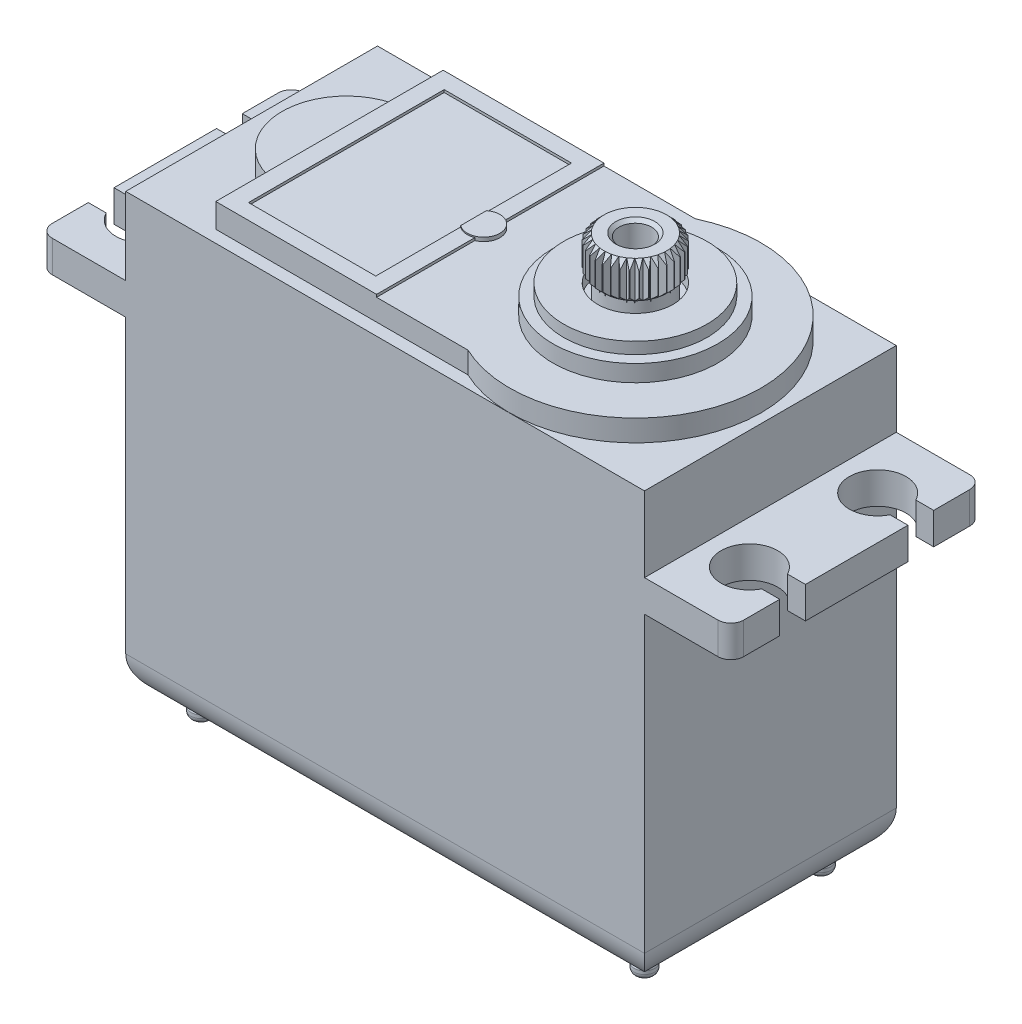
SolidWorks part; units mm, degrees
ref_plane "Front Plane" through (0, 0, 0) normal (0, 0, 1) x (1, 0, 0)
ref_plane "Top Plane" through (0, 0, 0) normal (0, 1, 0) x (1, 0, 0)
ref_plane "Right Plane" through (0, 0, 0) normal (1, 0, 0) x (0, 0, -1)
sketch "Sketch1" plane through (0, 0, 0) normal (0, 1, 0) x (1, 0, 0)
  line L1 (-18.6567, 11.3793) -> (21.6633, 11.3793)
  line L2 (-18.6567, 11.3793) -> (-18.6567, -8.1907)
  line L3 (-18.6567, -8.1907) -> (21.6633, -8.1907)
  line L4 (21.6633, 11.3793) -> (21.6633, -8.1907)
extrude "Boss-Extrude1" add sketch "Sketch1" along normal blind 35.37
sketch "Sketch2" plane through (21.6633, 0, 0) normal (1, 0, 0) x (0, 0, -1)
  line L0 (-8.1907, 0) -> (-8.1907, 3)
  line L1 (-8.1907, 35.37) -> (-8.1907, 0) construction
  line L2 (-8.1907, 3) -> (-5.1907, 0)
  line L3 (-8.1907, 0) -> (11.3793, 0) construction
  line L4 (-5.1907, 0) -> (-8.1907, 0)
  line L5 (1.5943, 0) -> (1.5943, 35.37) construction
  line L6 (-8.1907, 35.37) -> (11.3793, 35.37) construction
  line L7 (8.3793, 0) -> (11.3793, 0)
  line L8 (11.3793, 3) -> (8.3793, 0)
  line L9 (11.3793, 0) -> (11.3793, 3)
extrude "Cut-Extrude1" cut sketch "Sketch2" against normal up to next
sketch "Sketch3" plane through (0, 0, 8.1907) normal (0, 0, 1) x (1, 0, 0)
  line L0 (21.6633, 0) -> (18.6633, 0)
  line L1 (-18.6567, 0) -> (21.6633, 0) construction
  line L2 (18.6633, 0) -> (21.6633, 3)
  line L3 (21.6633, 35.37) -> (21.6633, 3) construction
  line L4 (21.6633, 3) -> (21.6633, 0)
  line L5 (1.5033, 35.37) -> (1.5033, 0) construction
  line L6 (-18.6567, 35.37) -> (21.6633, 35.37) construction
  line L7 (-18.6567, 3) -> (-18.6567, 0)
  line L8 (-15.6567, 0) -> (-18.6567, 3)
  line L9 (-18.6567, 0) -> (-15.6567, 0)
extrude "Cut-Extrude2" cut sketch "Sketch3" against normal up to next
fillet "Fillet2" radius 3 4 edges at (21.6633, 3, -1.5943) (1.5033, 3, 8.1907) (-18.6567, 3, -1.5943) (1.5033, 3, -11.3793)
sketch "Sketch5" plane through (21.6633, 0, 0) normal (1, 0, 0) x (0, 0, -1)
  line L0 (1.5943, 35.37) -> (1.5943, 29.53) construction
  line L1 (-8.1907, 35.37) -> (11.3793, 35.37) construction
  line L2 (-8.1907, 29.53) -> (1.5943, 29.53)
  line L3 (-8.1907, 35.37) -> (-8.1907, 4.2426) construction
  line L4 (1.5943, 29.53) -> (11.3793, 29.53)
  line L5 (11.3793, 35.37) -> (11.3793, 4.2426) construction
  line L6 (11.3793, 29.53) -> (11.3793, 27.07)
  line L7 (11.3793, 27.07) -> (-8.1907, 27.07)
  line L8 (-8.1907, 27.07) -> (-8.1907, 29.53)
extrude "Boss-Extrude2" add sketch "Sketch5" along normal blind 6.71
sketch "Sketch7" plane through (-18.6567, 0, 0) normal (-1, 0, 0) x (0, 0, 1)
  line L0 (-1.5943, 35.37) -> (-1.5943, 29.3613) construction
  line L1 (-11.3793, 29.3613) -> (-1.5943, 29.3613)
  line L2 (-1.5943, 29.3613) -> (8.1907, 29.3613)
  line L3 (8.1907, 29.3613) -> (8.1907, 26.9013)
  line L4 (8.1907, 26.9013) -> (-11.3793, 26.9013)
  line L5 (-11.3793, 26.9013) -> (-11.3793, 29.3613)
  line L6 (-11.3793, 35.37) -> (8.1907, 35.37) construction
  line L7 (8.1907, 35.37) -> (8.1907, 4.2426) construction
  line L8 (-11.3793, 35.37) -> (-11.3793, 4.2426) construction
extrude "Boss-Extrude3" add sketch "Sketch7" along normal blind 6.71
sketch "Sketch8" plane through (0, 29.53, 0) normal (0, 1, 0) x (1, 0, 0)
  line L0 (25.0183, 11.3793) -> (25.0183, 6.5793) construction
  line L1 (28.3733, 11.3793) -> (21.6633, 11.3793) construction
  line L2 (28.3733, 5.5793) -> (26.9779, 5.5793)
  line L3 (25.0183, -8.1907) -> (25.0183, -3.3907) construction
  line L4 (28.3733, -8.1907) -> (21.6633, -8.1907) construction
  line L5 (28.3733, 7.5793) -> (28.3733, 5.5793)
  line L6 (25.0183, 6.5793) -> (28.3733, 6.5793) construction
  line L7 (28.3733, 11.3793) -> (28.3733, -8.1907) construction
  line L8 (28.3733, 6.5793) -> (28.3733, 7.5793) construction
  line L9 (28.3733, 6.5793) -> (28.3733, 5.5793) construction
  line L10 (28.3733, 7.5793) -> (26.9779, 7.5793)
  line L11 (25.0183, -3.3907) -> (28.3733, -3.3907) construction
  line L12 (28.3733, -3.3907) -> (28.3733, -2.3907) construction
  line L13 (28.3733, -3.3907) -> (28.3733, -4.3907) construction
  line L14 (28.3733, -2.3907) -> (26.9779, -2.3907)
  line L15 (28.3733, -4.3907) -> (26.9779, -4.3907)
  line L16 (28.3733, -2.3907) -> (28.3733, -4.3907)
  line L17 (0, 0) -> (1.5, 0) construction
  line L18 (1.5, 0) -> (1.5, -13.7092) construction
  line L19 (-25.3733, -3.3907) -> (-25.3733, -4.3907) construction
  line L20 (-25.3733, -3.3907) -> (-25.3733, -2.3907) construction
  line L21 (-22.0183, -3.3907) -> (-25.3733, -3.3907) construction
  line L22 (-25.3733, 6.5793) -> (-25.3733, 5.5793) construction
  line L23 (-25.3733, 6.5793) -> (-25.3733, 7.5793) construction
  line L24 (-22.0183, 6.5793) -> (-25.3733, 6.5793) construction
  line L25 (-22.0183, -8.1907) -> (-22.0183, -3.3907) construction
  line L26 (-22.0183, 11.3793) -> (-22.0183, 6.5793) construction
  line L27 (-25.3733, -2.3907) -> (-25.3733, -4.3907)
  line L28 (-25.3733, -4.3907) -> (-23.9779, -4.3907)
  line L29 (-25.3733, -2.3907) -> (-23.9779, -2.3907)
  line L30 (-25.3733, 7.5793) -> (-23.9779, 7.5793)
  line L31 (-25.3733, 7.5793) -> (-25.3733, 5.5793)
  line L32 (-25.3733, 5.5793) -> (-23.9779, 5.5793)
  line L33 (-22.0183, 6.5793) -> (25.0183, 6.5793) construction
  line L34 (-19.8183, -3.3907) -> (-18.6668, -3.3907) construction
  line L35 (-22.0183, 6.5793) -> (-22.0183, -3.3907) construction
  line L38 (-22.0183, 6.5793) -> (25.0183, -3.3907) construction
  line L39 (-22.0183, -3.3907) -> (25.0183, 6.5793) construction
  line L40 (-25.3733, -8.1907) -> (28.3733, -8.1907) construction
  arc A0 (26.9779, 7.5793) -> (26.9779, 5.5793) centre (25.0183, 6.5793) ccw
  arc A1 (26.9779, -2.3907) -> (26.9779, -4.3907) centre (25.0183, -3.3907) ccw
  arc A2 (-23.9779, -2.3907) -> (-23.9779, -4.3907) centre (-22.0183, -3.3907) cw
  arc A3 (-23.9779, 7.5793) -> (-23.9779, 5.5793) centre (-22.0183, 6.5793) cw
  point P39 (1.5, 1.5943)
  dimension "D1" = 47.0366
  dimension "D2" = 9.97
  dimension "D3" = 53.7466
extrude "Cut-Extrude3" cut sketch "Sketch8" against normal up to next
sketch "Sketch9" plane through (0, 35.37, 0) normal (0, 1, 0) x (1, 0, 0)
  line L0 (6.9933, -8.1907) -> (6.9933, -7.2426) construction
  line L1 (-18.6567, 6.4311) -> (-12.6067, 6.4311) construction
  line L2 (6.9933, 11.3793) -> (6.9933, 10.4311) construction
  line L3 (-18.6567, -3.2426) -> (-12.6067, -3.2426) construction
  line L4 (-18.6567, -8.1907) -> (-18.6567, 11.3793) construction
  line L5 (-18.6567, 1.5943) -> (21.6633, 1.5943) construction
  line L6 (-12.6067, 10.4311) -> (6.9933, 10.4311)
  line L7 (-18.6567, 11.3793) -> (-18.6567, -8.1907) construction
  line L8 (-12.6067, -7.2426) -> (-12.6067, -3.2426)
  line L9 (21.6633, -8.1907) -> (21.6633, 11.3793) construction
  line L10 (-12.6067, 10.4311) -> (-12.6067, 6.4311)
  line L11 (-12.6067, -7.2426) -> (6.9933, -7.2426)
  line L12 (21.6633, 1.5943) -> (20.9438, 1.5943) construction
  line L13 (21.6633, 11.3793) -> (-18.6567, 11.3793) construction
  arc A0 (6.9933, 10.4311) -> (6.9933, -7.2426) centre (11.1697, 1.5943) cw
  arc A1 (-12.6067, 6.4311) -> (-12.6067, -3.2426) centre (-11.2767, 1.5943) ccw
extrude "Boss-Extrude4" add sketch "Sketch9" along normal blind 1.67
sketch "Sketch10" plane through (0, 37.04, 0) normal (0, 1, 0) x (1, 0, 0)
  circle A1 centre (11.1697, 1.5943) radius 6.415
extrude "Boss-Extrude5" add sketch "Sketch10" along normal blind 1.3
sketch "Sketch11" plane through (0, 38.34, 0) normal (0, 1, 0) x (-1, 0, 0)
  circle A2 centre (-11.1697, -1.5943) radius 5.575
extrude "Boss-Extrude6" add sketch "Sketch11" along normal blind 0.9
sketch "Sketch12" plane through (0, 39.24, 0) normal (0, 1, 0) x (1, 0, 0)
  circle A1 centre (11.1697, 1.5943) radius 2.925
extrude "Cut-Extrude4" cut sketch "Sketch12" against normal blind 1
sketch "Sketch13" plane through (0, 38.24, 0) normal (0, 1, 0) x (-1, 0, 0)
  circle A0 centre (-11.1697, -1.5943) radius 2.425
extrude "Boss-Extrude7" add sketch "Sketch13" along normal blind 1.5
sketch "Sketch14" plane through (0, 39.74, 0) normal (0, 1, 0) x (1, 0, 0)
  circle A0 centre (11.1697, 1.5943) radius 2.925
extrude "Boss-Extrude8" add sketch "Sketch14" along normal blind 2.86
sketch "Sketch15" plane through (0, 42.6, 0) normal (0, 1, 0) x (1, 0, 0)
  circle A0 centre (11.1697, 1.5943) radius 1.27
extrude "Cut-Extrude5" cut sketch "Sketch15" against normal blind 7
sketch "Sketch16" plane through (0, 37.04, 0) normal (0, 1, 0) x (1, 0, 0)
  line L0 (-12.6067, -7.2426) -> (6.9933, -7.2426) construction
  line L1 (-12.6067, 10.4311) -> (-0.1067, 10.4311)
  line L2 (-12.6067, 10.4311) -> (-12.6067, -7.2426)
  line L3 (-12.6067, -7.2426) -> (-0.1067, -7.2426)
  line L4 (-0.1067, 10.4311) -> (-0.1067, -7.2426)
  line L5 (-6.3168, 9.1673) -> (-6.3567, 10.4311) construction
  line L6 (-11.2628, 9.1673) -> (-1.3708, 9.1673)
  line L7 (-11.2628, 9.1673) -> (-11.2628, -6.0433)
  line L8 (-11.2628, -6.0433) -> (-1.3708, -6.0433)
  line L9 (-1.3708, 9.1673) -> (-1.3708, 1.562)
  line L10 (-11.2628, 1.562) -> (-12.6067, 1.5943) construction
  line L11 (-1.3708, 1.562) -> (-0.1067, 1.5943) construction
  line L12 (-6.3168, -6.0433) -> (-6.3567, -7.2426) construction
  line L13 (-1.3708, 1.562) -> (-1.3708, -6.0433)
extrude "Boss-Extrude9" add sketch "Sketch16" along normal blind 0.2
sketch "Sketch17" plane through (0, 37.24, 0) normal (0, 1, 0) x (-1, 0, 0)
  line L0 (1.3708, -1.562) -> (1.3708, -2.562)
  line L1 (1.3708, 6.0433) -> (1.3708, -9.1673) construction
  line L2 (1.3708, -1.562) -> (1.3708, -0.562)
  arc A0 (1.3708, -2.562) -> (1.3708, -0.562) centre (0.592, -1.562) cw
extrude "Boss-Extrude10" add sketch "Sketch17" along normal blind 0.1 and the other way blind 0.5
sketch "Sketch19" plane through (0, 42.6, 0) normal (0, 1, 0) x (1, 0, 0)
  line L0 (10.8404, 4.5007) -> (11.3402, 4.5143) construction
  line L1 (11.3402, 4.5143) -> (11.0903, 4.0075)
  line L2 (11.0903, 4.0075) -> (10.8404, 4.5007)
  line L3 (11.0903, 4.5075) -> (11.0903, 4.0075) construction
  line L4 (10.8404, 4.5007) -> (10.7613, 4.6463)
  line L5 (11.3402, 4.5143) -> (11.4053, 4.6463)
  line L6 (10.7613, 4.6463) -> (11.4053, 4.6463)
  circle A3 centre (11.1697, 1.5943) radius 2.925 construction
  circle A4 centre (11.1697, 1.5943) radius 2.925 construction
extrude "Cut-Extrude11" cut sketch "Sketch19" against normal blind 3
sketch "Sketch21" plane through (0, 0, 0) normal (0, -1, 0) x (1, 0, 0)
  line L0 (1.5033, 5.1907) -> (1.5033, -8.3793) construction
  line L1 (20.7846, 7.3121) -> (17.7846, 7.3121)
  line L2 (20.7846, 7.3121) -> (20.7846, 4.3121)
  line L3 (20.7846, 4.3121) -> (17.7846, 4.3121)
  line L4 (17.7846, 7.3121) -> (17.7846, 4.3121)
  line L5 (-15.6567, 5.1907) -> (18.6633, 5.1907) construction
  line L6 (-15.6567, -8.3793) -> (18.6633, -8.3793) construction
  line L7 (-15.6567, -1.5943) -> (18.6633, -1.5943) construction
  line L8 (-15.6567, -8.3793) -> (-15.6567, 5.1907) construction
  line L9 (18.6633, -8.3793) -> (18.6633, 5.1907) construction
  line L10 (17.7846, -10.5006) -> (17.7846, -7.5006)
  line L11 (20.7846, -7.5006) -> (17.7846, -7.5006)
  line L12 (20.7846, -10.5006) -> (20.7846, -7.5006)
  line L13 (20.7846, -10.5006) -> (17.7846, -10.5006)
  line L14 (-17.778, -7.5006) -> (-14.778, -7.5006)
  line L15 (-14.778, -10.5006) -> (-14.778, -7.5006)
  line L16 (-14.778, 7.3121) -> (-14.778, 4.3121)
  line L17 (-17.778, 4.3121) -> (-14.778, 4.3121)
  line L18 (-17.778, -10.5006) -> (-14.778, -10.5006)
  line L19 (-17.778, -10.5006) -> (-17.778, -7.5006)
  line L20 (-17.778, 7.3121) -> (-17.778, 4.3121)
  line L21 (-17.778, 7.3121) -> (-14.778, 7.3121)
extrude "Cut-Extrude12" cut sketch "Sketch21" against normal blind 1
fillet "Fillet4" radius 1 4 edges at (-14.778, 0.5, -7.5006) (-14.778, 0.5, 4.3121) (17.7846, 0.5, -7.5006) (17.7846, 0.5, 4.3121)
fillet "Fillet5" radius 1 4 edges at (-25.3667, 28.1313, 8.1907) (-25.3667, 28.1313, -11.3793) (28.3733, 28.3, -11.3793) (28.3733, 28.3, 8.1907)
chamfer "Chamfer2" distance 0.5 angle 45 2 edges at (11.2493, 42.6, 1.3297) (11.2493, 39.74, 1.3297)
chamfer "Chamfer3" distance 0.25 angle 45 1 edges at (11.1697, 42.6, -0.3243)
pattern_circular "CirPattern12" count 34 over 360 about axis through (11.1697, 42.6, -1.5943) along (0, -1, 0) of "Cut-Extrude11"
sketch "Sketch23" plane through (0, 1, 0) normal (0, -1, 0) x (1, 0, 0)
  line L0 (1.5033, 5.1907) -> (1.5033, -8.3793) construction
  line L1 (-14.7854, 5.1907) -> (17.792, 5.1907) construction
  line L2 (-14.7854, -8.3793) -> (17.792, -8.3793) construction
  line L3 (18.6633, -1.5943) -> (-15.6567, -1.5943) construction
  line L4 (18.6633, -7.508) -> (18.6633, 4.3195) construction
  line L5 (-15.6567, -7.508) -> (-15.6567, 4.3195) construction
  circle A0 centre (18.7344, -8.4503) radius 0.4237
  circle A1 centre (18.7344, 5.2618) radius 0.4237
  circle A2 centre (-15.7278, 5.2618) radius 0.4237
  circle A3 centre (-15.7278, -8.4503) radius 0.4237
extrude "Boss-Extrude12" add sketch "Sketch23" along normal blind 0.1
sketch "Sketch24" plane through (0, 0.9, 0) normal (0, -1, 0) x (1, 0, 0)
  line L0 (1.5033, 5.1907) -> (1.5033, -8.3793) construction
  line L1 (-14.7854, 5.1907) -> (17.792, 5.1907) construction
  line L2 (-14.7854, -8.3793) -> (17.792, -8.3793) construction
  line L3 (18.6633, -1.5943) -> (-15.6567, -1.5943) construction
  line L4 (18.6633, -7.508) -> (18.6633, 4.3195) construction
  line L5 (-15.6567, -7.508) -> (-15.6567, 4.3195) construction
  circle A0 centre (18.7344, -8.4503) radius 0.8
  circle A1 centre (18.7344, 5.2618) radius 0.8
  circle A2 centre (-15.7278, 5.2618) radius 0.8
  circle A3 centre (-15.7278, -8.4503) radius 0.8
extrude "Boss-Extrude13" add sketch "Sketch24" along normal blind 0.9
fillet "Fillet8" radius 0.45 4 edges at (18.7344, 0, -9.2503) (-15.7278, 0, -7.6503) (-15.7278, 0, 4.4618) (18.7344, 0, 6.0618)
fillet "Fillet9" radius 0.2 4 edges at (-15.7278, 0.9, -7.6503) (-15.7278, 0.9, 4.4618) (18.7344, 0.9, 6.0618) (18.7344, 0.9, -9.2503)
sketch "Sketch25" plane through (0, 0, 0) normal (0, -1, 0) x (1, 0, 0)
  line L0 (18.0844, 5.3868) -> (18.0844, 5.1368)
  line L1 (18.6094, 4.6118) -> (18.8594, 4.6118)
  line L2 (18.0844, 5.3868) -> (18.6094, 5.3868)
  line L3 (18.6094, 5.3868) -> (18.6094, 5.9118)
  line L4 (19.3844, 5.1368) -> (19.3844, 5.3868)
  line L5 (18.8594, 5.9118) -> (18.6094, 5.9118)
  line L6 (1.5033, 5.1907) -> (1.5033, -8.3793) construction
  line L7 (-14.7854, 5.1907) -> (17.792, 5.1907) construction
  line L8 (-14.7854, -8.3793) -> (17.792, -8.3793) construction
  line L9 (18.6633, -1.5943) -> (-15.6567, -1.5943) construction
  line L10 (18.6633, -7.508) -> (18.6633, 4.3195) construction
  line L11 (-15.6567, -7.508) -> (-15.6567, 4.3195) construction
  line L12 (18.6094, -8.3253) -> (18.0844, -8.3253)
  line L13 (18.6094, -7.8003) -> (18.6094, -8.3253)
  line L14 (18.8594, -8.3253) -> (18.8594, -7.8003)
  line L15 (19.3844, -8.3253) -> (18.8594, -8.3253)
  line L16 (18.8594, -8.5753) -> (19.3844, -8.5753)
  line L17 (18.8594, 5.9118) -> (18.8594, 5.3868)
  line L18 (18.8594, 5.3868) -> (19.3844, 5.3868)
  line L19 (18.8594, -9.1003) -> (18.8594, -8.5753)
  line L20 (19.3844, 5.1368) -> (18.8594, 5.1368)
  line L21 (18.8594, 5.1368) -> (18.8594, 4.6118)
  line L22 (18.8594, -9.1003) -> (18.6094, -9.1003)
  line L23 (18.6094, 4.6118) -> (18.6094, 5.1368)
  line L24 (18.6094, 5.1368) -> (18.0844, 5.1368)
  line L25 (19.3844, -8.3253) -> (19.3844, -8.5753)
  line L26 (18.6094, -8.5753) -> (18.6094, -9.1003)
  line L27 (18.0844, -8.5753) -> (18.6094, -8.5753)
  line L28 (18.6094, -7.8003) -> (18.8594, -7.8003)
  line L29 (18.0844, -8.5753) -> (18.0844, -8.3253)
  line L30 (-15.0778, -8.5753) -> (-15.0778, -8.3253)
  line L31 (-15.6028, -7.8003) -> (-15.8528, -7.8003)
  line L32 (-15.0778, -8.5753) -> (-15.6028, -8.5753)
  line L33 (-15.6028, -8.5753) -> (-15.6028, -9.1003)
  line L34 (-16.3778, -8.3253) -> (-16.3778, -8.5753)
  line L35 (-15.6028, 5.1368) -> (-15.0778, 5.1368)
  line L36 (-15.6028, 4.6118) -> (-15.6028, 5.1368)
  line L37 (-15.8528, -9.1003) -> (-15.6028, -9.1003)
  line L38 (-15.8528, 5.1368) -> (-15.8528, 4.6118)
  line L39 (-16.3778, 5.1368) -> (-15.8528, 5.1368)
  line L40 (-15.8528, -9.1003) -> (-15.8528, -8.5753)
  line L41 (-15.8528, 5.3868) -> (-16.3778, 5.3868)
  line L42 (-15.8528, 5.9118) -> (-15.8528, 5.3868)
  line L43 (-15.8528, -8.5753) -> (-16.3778, -8.5753)
  line L44 (-16.3778, -8.3253) -> (-15.8528, -8.3253)
  line L45 (-15.8528, -8.3253) -> (-15.8528, -7.8003)
  line L46 (-15.6028, -7.8003) -> (-15.6028, -8.3253)
  line L47 (-15.6028, -8.3253) -> (-15.0778, -8.3253)
  line L48 (-15.8528, 5.9118) -> (-15.6028, 5.9118)
  line L49 (-16.3778, 5.1368) -> (-16.3778, 5.3868)
  line L50 (-15.6028, 5.3868) -> (-15.6028, 5.9118)
  line L51 (-15.0778, 5.3868) -> (-15.6028, 5.3868)
  line L52 (-15.6028, 4.6118) -> (-15.8528, 4.6118)
  line L53 (-15.0778, 5.3868) -> (-15.0778, 5.1368)
extrude "Cut-Extrude14" cut sketch "Sketch25" against normal blind 0.6
sketch "Sketch26" plane through (-18.6567, 0, 0) normal (-1, 0, 0) x (0, 0, 1)
  line L0 (8.1907, 26.9013) -> (8.1907, 4.2426)
  line L2 (-11.3793, 4.2426) -> (8.1907, 4.2426)
